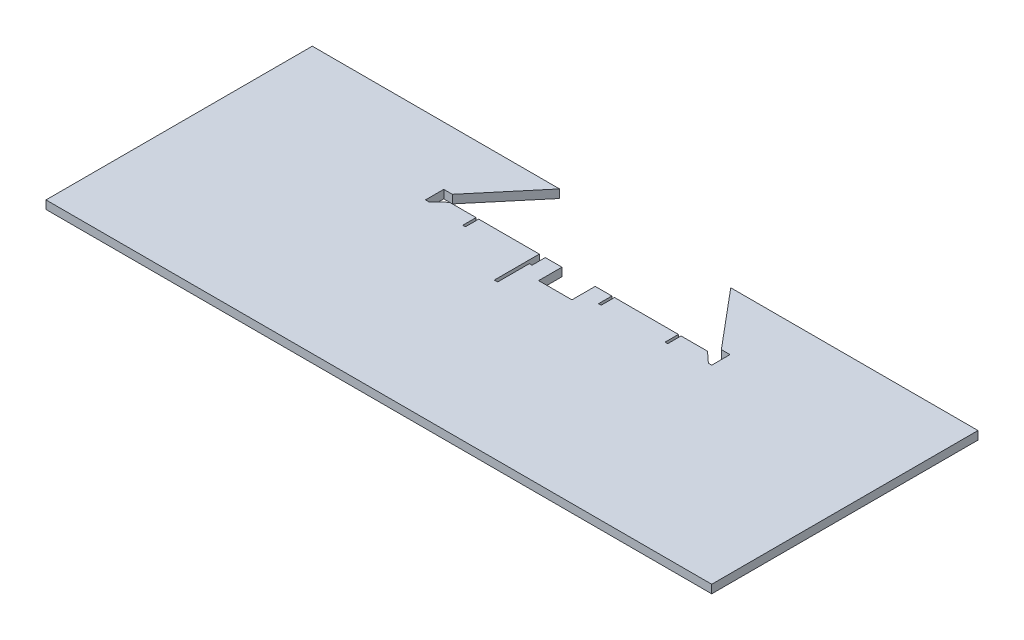
SolidWorks part; units mm, degrees
material "Depron"
ref_plane "Front Plane" through (0, 0, 0) normal (0, 0, 1) x (1, 0, 0)
ref_plane "Top Plane" through (0, 0, 0) normal (0, 1, 0) x (1, 0, 0)
ref_plane "Right Plane" through (0, 0, 0) normal (1, 0, 0) x (0, 0, -1)
sketch "Sketch1" plane through (0, 0, 0) normal (0, 1, 0) x (1, 0, 0)
  line L0 (32.6619, 101.6) -> (127, 101.6)
  line L1 (-127, 0) -> (127, 0)
  line L2 (-127, 0) -> (-127, 101.6)
  line L3 (-127, 101.6) -> (-32.6619, 101.6)
  line L4 (127, 0) -> (127, 101.6)
  line L5 (0, -898.4) -> (0, 49101.6) construction
  line L6 (-53.975, 76.2) -> (-32.6619, 101.6)
  line L7 (-53.975, 76.2) -> (53.975, 76.2)
  line L8 (53.975, 76.2) -> (32.6619, 101.6)
  line L9 (-1003.9539, 76.2) -> (48996.0461, 76.2) construction
  point P11 (0, 76.2)
  dimension "D1" = 101.6
  dimension "D2" = 254
  dimension "D4" = 107.95
  dimension "D6" = 25.4
extrude "Boss-Extrude1" add sketch "Sketch1" along normal blind 3.175
sketch "Sketch2" plane through (0, 3.175, 0) normal (0, 1, 0) x (-1, 0, 0)
  line L0 (0, 0) -> (0, -134.62) construction
  line L1 (127, 0) -> (-127, 0) construction
  line L2 (-53.975, -76.2) -> (53.975, -76.2) construction
  line L3 (39.116, -76.2) -> (38.1, -76.2)
  line L4 (39.116, -76.2) -> (39.116, -71.12)
  line L5 (39.116, -71.12) -> (38.1, -71.12)
  line L6 (38.1, -76.2) -> (38.1, -71.12)
  line L7 (13.716, -76.2) -> (12.7, -76.2)
  line L8 (-53.975, -76.2) -> (53.975, -76.2) construction
  line L9 (13.716, -71.12) -> (12.7, -71.12)
  line L10 (12.7, -76.2) -> (12.7, -71.12)
  line L11 (-12.7, -76.2) -> (-12.7, -71.12)
  line L12 (-13.716, -71.12) -> (-12.7, -71.12)
  line L13 (-13.716, -76.2) -> (-13.716, -71.12)
  line L14 (-13.716, -76.2) -> (-12.7, -76.2)
  line L15 (-38.1, -76.2) -> (-38.1, -71.12)
  line L16 (-39.116, -71.12) -> (-38.1, -71.12)
  line L17 (-39.116, -76.2) -> (-39.116, -71.12)
  line L18 (-39.116, -76.2) -> (-38.1, -76.2)
  line L19 (6.35, -76.2) -> (-6.35, -76.2)
  line L20 (13.716, -76.2) -> (14.986, -76.2)
  line L21 (13.716, -71.12) -> (13.716, -59.055)
  line L22 (13.716, -59.055) -> (14.986, -59.055)
  line L23 (14.986, -76.2) -> (14.986, -59.055)
  line L24 (6.35, -76.2) -> (6.35, -67.31)
  line L25 (6.35, -67.31) -> (-6.35, -67.31)
  line L26 (-6.35, -76.2) -> (-6.35, -67.31)
  line L27 (-53.975, -76.2) -> (-51.3109, -79.375)
  line L28 (53.34, -80.01) -> (54.61, -80.01) construction
  line L29 (53.34, -80.01) -> (53.34, -72.39) construction
  line L30 (53.34, -72.39) -> (54.61, -72.39)
  line L31 (54.61, -80.01) -> (54.61, -72.39) construction
  line L32 (53.34, -80.01) -> (54.61, -72.39) construction
  line L33 (53.34, -72.39) -> (54.61, -80.01) construction
  line L34 (-53.34, -76.2) -> (-53.975, -76.2)
  line L35 (-53.34, -72.39) -> (-49.1905, -76.2)
  line L36 (-53.34, -72.39) -> (-54.61, -72.39)
  line L37 (53.975, -76.2) -> (32.6619, -101.6) construction
  line L38 (53.975, -76.2) -> (51.3109, -79.375)
  line L39 (51.3109, -79.375) -> (54.61, -79.375)
  line L40 (54.61, -79.375) -> (54.61, -72.39)
  line L41 (53.34, -72.39) -> (49.1905, -76.2)
  line L42 (53.34, -76.2) -> (53.975, -76.2)
  line L43 (-54.61, -79.375) -> (-54.61, -72.39)
  line L44 (-51.3109, -79.375) -> (-54.61, -79.375)
  point P31 (0, -67.31)
  point P32 (53.975, -76.2)
  line M6 (-53.975, -76.2) -> (53.975, -76.2)
  line M38 (-32.6619, -101.6) -> (-53.975, -76.2)
  line M39 (53.975, -76.2) -> (32.6619, -101.6)
  dimension "D1" = 1.016
  dimension "D2" = 5.08
  dimension "D3" = 1.016
  dimension "D4" = 5.08
  dimension "D5" = 1.27
  dimension "D6" = 17.145
  dimension "D7" = 12.7
  dimension "D8" = 38.1
  dimension "D9" = 12.7
  dimension "D10" = 8.89
  dimension "D11" = 1.27
  dimension "D12" = 7.62
  dimension "D13" = 3.175
  dimension "D14" = 4.7845
ref_plane "Center Plane" through (0, 0, 0) normal (1, 0, 0) x (0, 0, -1)
sketch "Sketch3" plane through (0, 3.175, 0) normal (0, 1, 0) x (1, 0, 0)
  line L0 (-38.608, 71.12) -> (-38.608, 76.2)
  line L1 (-39.116, 71.12) -> (-38.1, 71.12) construction
  line L2 (-39.116, 76.2) -> (-38.1, 76.2) construction
  line L3 (-14.351, 76.2) -> (-14.351, 59.055)
  line L4 (-13.716, 76.2) -> (-14.986, 76.2) construction
  line L5 (-13.716, 59.055) -> (-14.986, 59.055) construction
  line L6 (-13.208, 71.12) -> (-13.208, 76.2)
  line L7 (-13.716, 71.12) -> (-12.7, 71.12) construction
  line L8 (-13.716, 76.2) -> (-12.7, 76.2) construction
  line L9 (-6.35, 76.2) -> (-6.35, 67.31)
  line L10 (-6.35, 67.31) -> (6.35, 67.31)
  line L11 (6.35, 67.31) -> (6.35, 76.2)
  line L12 (13.208, 71.12) -> (13.208, 76.2)
  line L13 (13.716, 71.12) -> (12.7, 71.12) construction
  line L14 (13.716, 76.2) -> (12.7, 76.2) construction
  line L15 (38.608, 71.12) -> (38.608, 76.2)
  line L16 (39.116, 71.12) -> (38.1, 71.12) construction
  line L17 (39.116, 76.2) -> (38.1, 76.2) construction
extrude "Cut-Extrude1" cut sketch "Sketch2" against normal up to surface (3.175 mm away) contours L6 L4 L5 M6 | L23 L22 L21 L9 L10 M6 | L26 L24 L25 M6 | L13 L11 L12 M6 | L17 L15 L16 M6 | L39 L40 L30 M6 M39 | L44 L36 L43 M38 M6 region at (52.9708, 3.175, -75.8259) region at (38.608, 3.175, -73.66) region at (13.208, 3.175, -73.66) region at (0, 3.175, -71.755) region at (-14.132, 3.175, -68.7834) region at (-38.608, 3.175, -73.66) region at (-52.9708, 3.175, -75.8259) up to face at (0, 0, -69.85)
